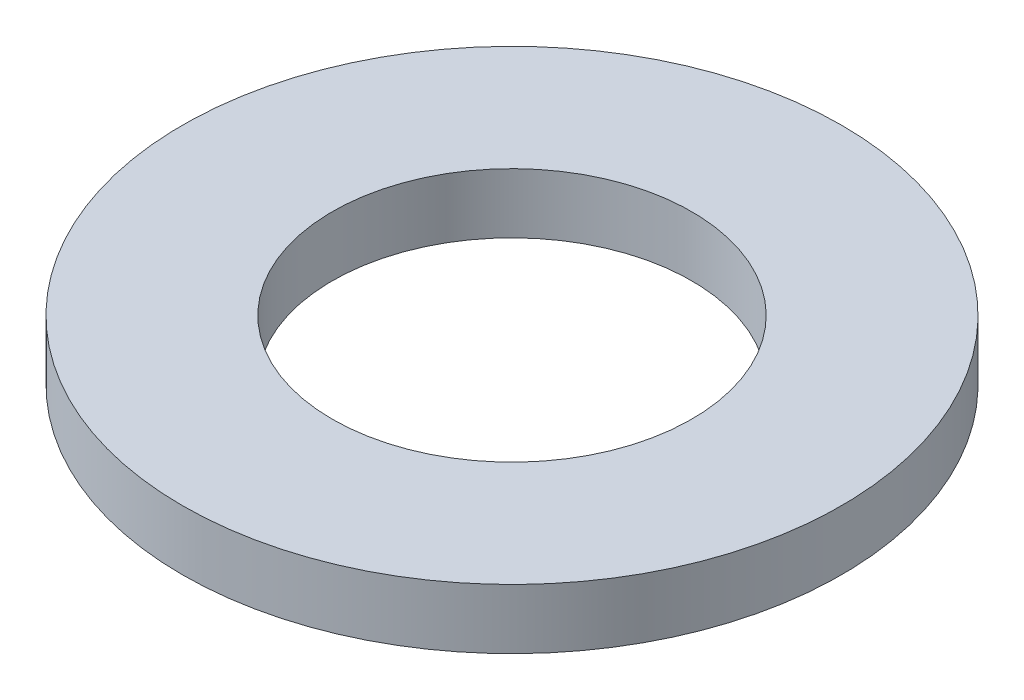
SolidWorks part; units mm, degrees
material "201 Stal nierdzewna odprężona (SS)"
ref_plane "Płaszczyzna przednia" through (0, 0, 0) normal (0, 0, 1) x (1, 0, 0)
ref_plane "Płaszczyzna górna" through (0, 0, 0) normal (0, 1, 0) x (1, 0, 0)
ref_plane "Płaszczyzna prawa" through (0, 0, 0) normal (1, 0, 0) x (0, 0, -1)
sketch "Szkic1" plane through (0, 0, 0) normal (0, 1, 0) x (1, 0, 0)
  circle A0 centre (0, 0) radius 6
  circle A1 centre (0, 0) radius 11
  dimension "D1" = 12
  dimension "D2" = 22
extrude "Dodanie-wyciągnięcie1" add sketch "Szkic1" along normal blind 2
